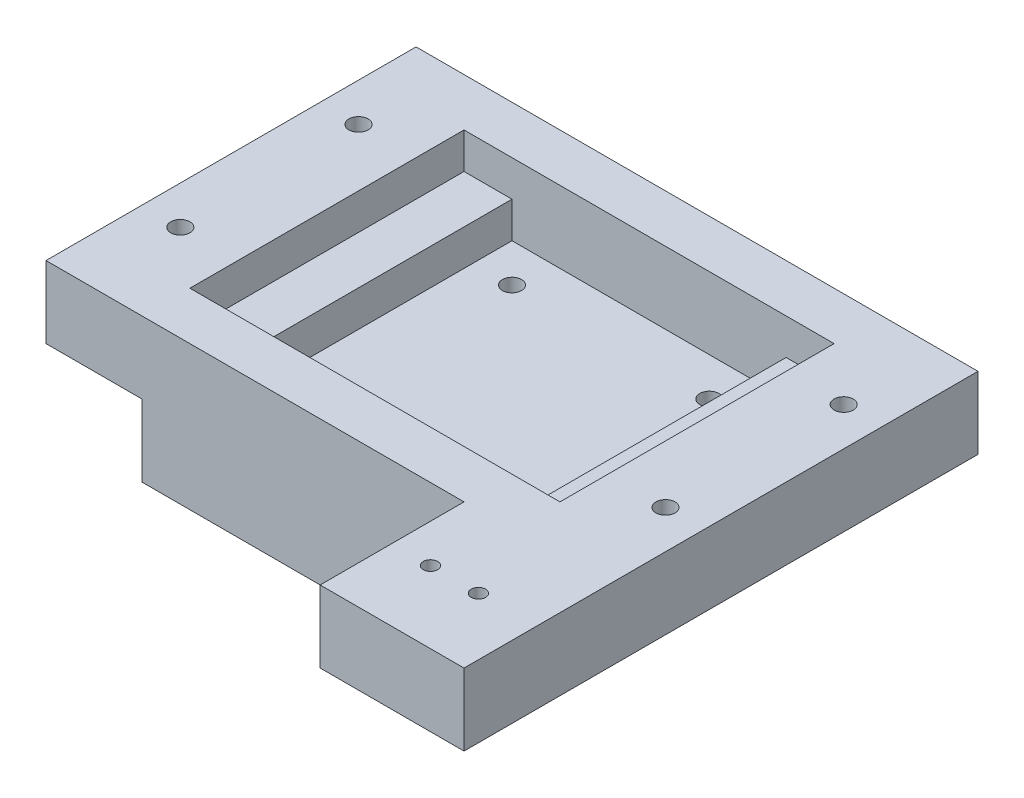
SolidWorks part; units mm, degrees
ref_plane "Front Plane" through (0, 0, 0) normal (0, 0, 1) x (1, 0, 0)
ref_plane "Top Plane" through (0, 0, 0) normal (0, 1, 0) x (1, 0, 0)
ref_plane "Right Plane" through (0, 0, 0) normal (1, 0, 0) x (0, 0, -1)
sketch "Croquis1" plane through (0, 0, 0) normal (0, 1, 0) x (1, 0, 0)
  line L0 (0, 38.575) -> (0, -38.575) construction
  line L1 (-38.575, -38.575) -> (38.575, -38.575)
  line L2 (-38.575, -38.575) -> (-38.575, 38.575)
  line L3 (-38.575, 38.575) -> (38.575, 38.575)
  line L4 (38.575, -38.575) -> (38.575, 38.575)
  line L5 (-38.575, 0) -> (38.575, 0) construction
  dimension "D1" = 38.575
  dimension "D2" = 38.575
  dimension "D3" = 38.575
  dimension "D4" = 38.575
extrude "Saliente-Extruir1" add sketch "Croquis1" along normal blind 15
sketch "Croquis4" plane through (0, 15, 0) normal (0, 1, 0) x (1, 0, 0)
  line L0 (-28.575, -38.575) -> (-28.575, 38.575)
  line L1 (-38.575, -38.575) -> (38.575, -38.575) construction
  line L2 (38.575, 38.575) -> (-38.575, 38.575) construction
  line L3 (-28.575, 38.575) -> (-38.575, 38.575)
  line L4 (-38.575, 38.575) -> (-38.575, -38.575)
  line L5 (-38.575, -38.575) -> (-28.575, -38.575)
  line L6 (-38.575, 38.575) -> (-58.575, 38.575)
  line L7 (-58.575, 38.575) -> (-58.575, -38.575)
  line L8 (-58.575, -38.575) -> (-38.575, -38.575)
  line M7 (-38.575, 38.575) -> (-38.575, -38.575)
  line M8 (-38.575, -38.575) -> (38.575, -38.575)
  line M10 (38.575, 38.575) -> (-38.575, 38.575)
  dimension "D1" = 20
  dimension "D2" = 10
extrude "Saliente-Extruir2" add sketch "Croquis4" along normal blind 7.5 contours L0 M8 M10 M7 region at (-33.575, 15, 0)
extrude "Saliente-Extruir3" add sketch "Croquis4<3>" along normal blind 15 contours L7 L8 L6 M7 region at (-48.575, 15, 0)
sketch "Croquis4<3>" plane through (0, 15, 0) normal (0, 1, 0) x (1, 0, 0) same geometry as "Croquis4"
ref_plane "Plano1" through (0, 0, 0) normal (-1, 0, 0) x (0, 0, 1)
mirror "Simetría1" about plane through (0, 0, 0) normal (-1, 0, 0) of "Saliente-Extruir3", "Saliente-Extruir2"
sketch "Croquis5" plane through (0, 0, 38.575) normal (0, 0, 1) x (1, 0, 0)
  line L0 (-58.575, 30) -> (-38.575, 30)
  line L9 (38.575, 30) -> (58.575, 30)
  line L10 (58.575, 30) -> (58.575, 15)
  line L11 (58.575, 15) -> (38.575, 15)
  line L12 (38.575, 15) -> (38.575, 0)
  line L13 (38.575, 0) -> (-38.575, 0)
  line L14 (-38.575, 0) -> (-38.575, 15)
  line L15 (-38.575, 15) -> (-58.575, 15)
  line L16 (-58.575, 15) -> (-58.575, 30)
  line L17 (-38.575, 30) -> (38.575, 30)
extrude "Saliente-Extruir4" add sketch "Croquis5" against normal blind 10
sketch "Croquis7" plane through (0, 15, 0) normal (0, 1, 0) x (1, 0, 0)
  line L0 (28.575, 38.575) -> (-28.575, 38.575) construction
  line L1 (28.575, -28.575) -> (28.575, 38.575) construction
  line L2 (-28.575, -28.575) -> (-28.575, 38.575) construction
  line L3 (-28.575, -38.575) -> (28.575, -38.575) construction
  circle A0 centre (20.575, 20.575) radius 2
  circle A1 centre (-20.575, 20.575) radius 2
  circle A2 centre (20.575, -20.575) radius 2
  circle A3 centre (-20.575, -20.575) radius 2
  dimension "D2" = 8
  dimension "D4" = 18
  dimension "D5" = 4
  dimension "D6" = 4
  dimension "D8" = 8
  dimension "D9" = 4
  dimension "D10" = 18
  dimension "D12" = 4
  dimension "D1" = 18
  dimension "D3" = 8
  dimension "D7" = 18
  dimension "D11" = 8
extrude "Cortar-Extruir2" cut sketch "Croquis7" against normal blind 50
sketch "Croquis8" plane through (0, 30, 0) normal (0, 1, 0) x (1, 0, 0)
  line L0 (-38.575, 38.575) -> (-58.575, 38.575) construction
  line L1 (-38.575, -28.575) -> (38.575, -28.575) construction
  line L2 (-58.575, 38.575) -> (-58.575, -38.575) construction
  line L3 (58.575, 38.575) -> (58.575, -38.575) construction
  line L4 (38.575, 38.575) -> (58.575, 38.575) construction
  circle A0 centre (50.575, 18.575) radius 2
  circle A1 centre (50.575, -18.575) radius 2
  circle A2 centre (-50.575, 18.575) radius 2
  circle A3 centre (-50.575, -18.575) radius 2
  dimension "D1" = 4
  dimension "D2" = 4
  dimension "D3" = 4
  dimension "D4" = 4
  dimension "D5" = 20
  dimension "D6" = 10
  dimension "D7" = 8
  dimension "D8" = 8
  dimension "D9" = 8
  dimension "D10" = 20
  dimension "D11" = 10
  dimension "D12" = 8
extrude "Cortar-Extruir3" cut sketch "Croquis8" against normal blind 40
ref_plane "Plano2" through (0, 0, 0) normal (0, 0, -1) x (-1, 0, 0)
mirror "Simetría2" about plane through (0, 0, 0) normal (0, 0, -1) of "Saliente-Extruir4"
sketch "Croquis9" plane through (0, 0, 38.575) normal (0, 0, 1) x (1, 0, 0)
  line L0 (-58.575, 30) -> (-58.575, 15)
  line L1 (-58.575, 15) -> (58.575, 15)
  line L2 (58.575, 15) -> (58.575, 30)
  line L3 (58.575, 30) -> (-58.575, 30)
extrude "Saliente-Extruir5" add sketch "Croquis9" along normal blind 30
sketch "Croquis10" plane through (0, 30, 0) normal (0, 1, 0) x (1, 0, 0)
  line L0 (28.575, -68.575) -> (28.575, -38.575)
  line L1 (58.575, -68.575) -> (-58.575, -68.575) construction
  line L2 (28.575, -38.575) -> (-58.575, -38.575)
  line L3 (-58.575, 38.575) -> (-58.575, -68.575) construction
  line L4 (-58.575, -38.575) -> (-58.575, -68.575)
  line L5 (-58.575, -68.575) -> (28.575, -68.575)
  line L6 (38.575, -28.575) -> (-38.575, -28.575) construction
  line L7 (58.575, 38.575) -> (58.575, -68.575) construction
  dimension "D1" = 10
  dimension "D2" = 30
extrude "Cortar-Extruir4" cut sketch "Croquis10" against normal blind 40
sketch "Croquis11" plane through (0, 30, 0) normal (0, 1, 0) x (1, 0, 0)
  line L0 (28.575, -68.575) -> (28.575, -38.575) construction
  line L1 (58.575, -68.575) -> (28.575, -68.575) construction
  circle A0 centre (36.575, -53.575) radius 1.5
  circle A1 centre (46.575, -53.575) radius 1.5
  dimension "D2" = 3
  dimension "D3" = 3
  dimension "D1" = 10
  dimension "D4" = 8
  dimension "D5" = 15
  dimension "D6" = 15
extrude "Cortar-Extruir5" cut sketch "Croquis11" against normal blind 10
sketch "Croquis12" plane through (0, 0, -38.575) normal (0, 0, -1) x (-1, 0, 0)
  line L0 (0, 0) -> (0, 30) construction
  line L1 (-38.575, 0) -> (38.575, 0) construction
  line L2 (-58.575, 30) -> (58.575, 30) construction
  circle A0 centre (0, 20) radius 1.25
  point P6 (0, 0)
  dimension "D1" = 2.5
  dimension "D2" = 20
extrude "Cortar-Extruir6" cut sketch "Croquis12" against normal blind 4.3
